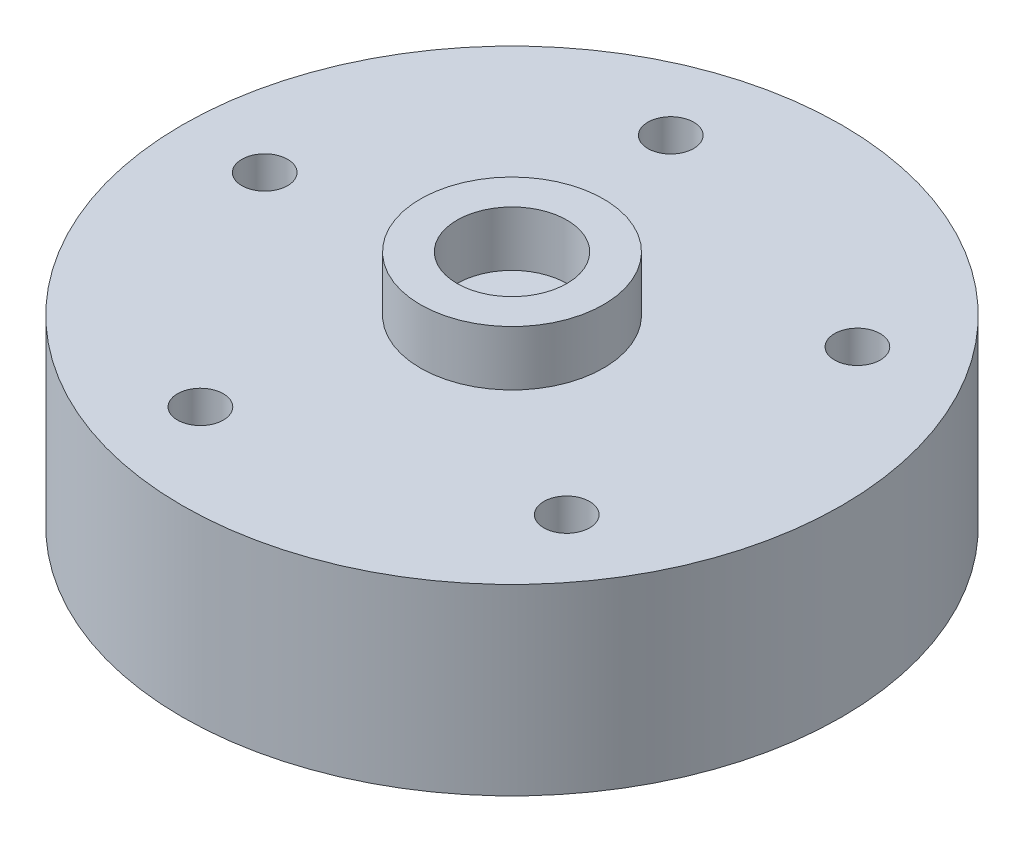
SolidWorks part; units mm, degrees
ref_plane "Front Plane" through (0, 0, 0) normal (0, 0, 1) x (1, 0, 0)
ref_plane "Top Plane" through (0, 0, 0) normal (0, 1, 0) x (1, 0, 0)
ref_plane "Right Plane" through (0, 0, 0) normal (1, 0, 0) x (0, 0, -1)
sketch "Sketch1" plane through (0, 0, 0) normal (0, 1, 0) x (1, 0, 0)
  line L0 (-13.5, 0) -> (13.5, 0) construction
  circle A0 centre (0, 0) radius 16
  circle A1 centre (0, 0) radius 13.5
  circle A2 centre (0, 0) radius 1.25
  circle A3 centre (-13.5, 0) radius 1.25
  circle A4 centre (-4.1717, 12.8393) radius 1.25
  circle A5 centre (10.9217, 7.9351) radius 1.25
  circle A6 centre (10.9217, -7.9351) radius 1.25
  circle A7 centre (-4.1717, -12.8393) radius 1.25
  point P19 (0, 0)
  dimension "D1" = 32
  dimension "D2" = 2.5
  dimension "D3" = 2.5
  dimension "D4" = 2.5
  dimension "D5" = 5
extrude "Boss-Extrude1" add sketch "Sketch1" along normal blind 2 and the other way blind 3 contours A0 A7 A1 A3 A4 A5 A6 | L0 A3 A1 A7 A6 A2 | A3 L0 A2 A1 A5 A4 region at (0, 0, -5.7246) region at (0, 0, 5.7246) region at (-15.5475, 0, 0)
sketch "Sketch2" plane through (0, 2, 0) normal (0, 1, 0) x (1, 0, 0)
  circle A0 centre (0, 0) radius 3
  circle A1 centre (0, 0) radius 5
  dimension "D1" = 6
  dimension "D2" = 2
extrude "Boss-Extrude3" add sketch "Sketch2" along normal blind 3 contours A1 A0 region at (-4.8586, 2, 0)
sketch "Sketch4" plane through (0, 2, 0) normal (0, 1, 0) x (1, 0, 0)
  circle A0 centre (0, 0) radius 2
sketch "Sketch5" plane through (0, -3, 0) normal (0, -1, 0) x (1, 0, 0)
  circle A0 centre (0, 0) radius 2.75
  dimension "D1" = 5.5
extrude "Cut-Extrude2" cut sketch "Sketch5" against normal blind 1
sketch "Sketch6" plane through (0, -3, 0) normal (0, -1, 0) x (1, 0, 0)
  circle A0 centre (0, 0) radius 16
  circle A1 centre (0, 0) radius 11
  circle A2 centre (0, 0) radius 16 construction
  circle A3 centre (-13.5, 0) radius 1.25
  circle A4 centre (-4.1717, 12.8393) radius 1.25
  circle A5 centre (10.9217, 7.9351) radius 1.25
  circle A6 centre (10.9217, -7.9351) radius 1.25
  circle A7 centre (-4.1717, -12.8393) radius 1.25
  point P20 (0, 0)
  dimension "D1" = 5
  dimension "D3" = 2.5
  dimension "D2" = 5
extrude "Boss-Extrude4" add sketch "Sketch6" along normal blind 5
sketch "Sketch7" plane through (0, 2, 0) normal (0, 1, 0) x (1, 0, 0)
  circle A0 centre (0, 0) radius 16
  circle A1 centre (0, 0) radius 18
  dimension "D1" = 2
extrude "Boss-Extrude5" add sketch "Sketch7" against normal blind 10
sketch "Sketch8" plane through (0, -2, 0) normal (0, -1, 0) x (1, 0, 0)
  circle A0 centre (0, 0) radius 2
extrude "Cut-Extrude3" cut sketch "Sketch8" against normal blind 3
sketch "Sketch9" plane through (0, -3, 0) normal (0, -1, 0) x (1, 0, 0)
  circle A0 centre (0, 0) radius 3.75
  dimension "D1" = 7.5
extrude "Cut-Extrude4" cut sketch "Sketch9" against normal blind 2
